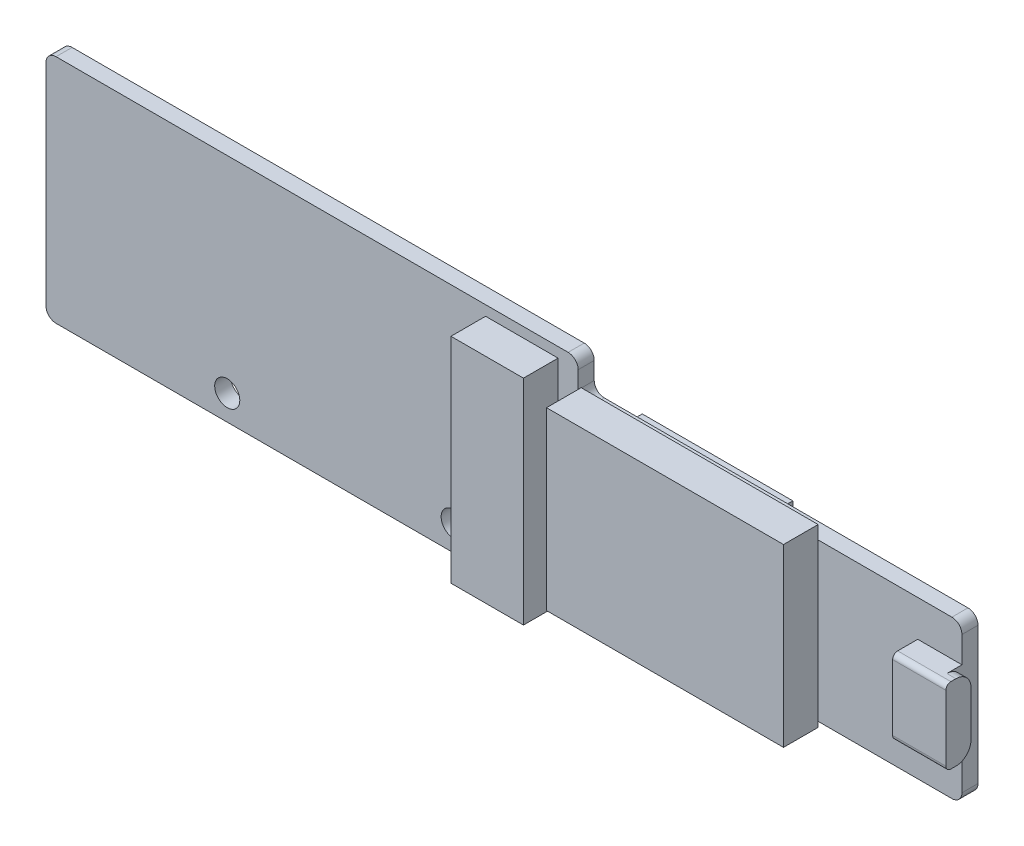
SolidWorks part; units mm, degrees
ref_plane "Front Plane" through (0, 0, 0) normal (0, 0, 1) x (1, 0, 0)
ref_plane "Top Plane" through (0, 0, 0) normal (0, 1, 0) x (1, 0, 0)
ref_plane "Right Plane" through (0, 0, 0) normal (1, 0, 0) x (0, 0, -1)
sketch "Sketch1" plane through (0, 0, 0) normal (0, 0, 1) x (1, 0, 0)
  line L0 (53, 19.27) -> (63.0723, 19.27) construction
  line L1 (0, 0) -> (53, 0)
  line L2 (0, 0) -> (0, 23)
  line L3 (0, 23) -> (53, 23)
  line L4 (53, 0) -> (53, 3.62)
  line L5 (47.5491, 11.445) -> (74.8048, 11.445) construction
  line L6 (53, 3.62) -> (63.0723, 3.62) construction
  line L7 (53, 19.27) -> (53, 23)
  line L8 (53, 19.27) -> (91.22, 19.27)
  line L10 (53, 3.62) -> (91.22, 3.62)
  line L11 (91.22, 19.27) -> (91.22, 3.62)
  circle A0 centre (40.6, 2.5) radius 1.25
  circle A1 centre (18.05, 2.5) radius 1.25
  dimension "D8" = 2.5
  dimension "D9" = 12.4
  dimension "D10" = 22.55
  dimension "D11" = 2.5
  dimension "D12" = 12.4
  dimension "D1" = 3.73
  dimension "D2" = 91.22
  dimension "D3" = 53
  dimension "D4" = 23
  dimension "D5" = 15.65
  dimension "D6" = 3.62
  dimension "D7" = 19.38
extrude "Boss-Extrude2" add sketch "Sketch1" along normal blind 1.6
sketch "Sketch2" plane through (0, 0, 0) normal (0, 0, -1) x (-1, 0, 0)
  line L0 (-91.22, 3.62) -> (-91.22, 19.27) construction
  line L1 (-72.12, 19.12) -> (-57.12, 19.12)
  line L2 (-72.12, 19.12) -> (-72.12, 3.77)
  line L3 (-72.12, 3.77) -> (-57.12, 3.77)
  line L4 (-57.12, 19.12) -> (-57.12, 3.77)
  line L5 (-72.12, 19.12) -> (-57.12, 3.77) construction
  line L6 (-72.12, 3.77) -> (-57.12, 19.12) construction
  line L7 (-91.22, 19.27) -> (-53, 19.27) construction
  line L8 (-53, 3.62) -> (-91.22, 3.62) construction
  point P0 (-64.62, 11.445)
  dimension "D1" = 34.1
  dimension "D2" = 15.5
  dimension "D3" = 0.15
  dimension "D4" = 0.15
extrude "Boss-Extrude3" add sketch "Sketch2" along normal blind 0.66
sketch "Sketch3" plane through (0, 0, 1.6) normal (0, 0, 1) x (1, 0, 0)
  line L1 (86.82, 15.66) -> (92.12, 15.66)
  line L2 (86.82, 15.66) -> (86.82, 8.12)
  line L3 (86.82, 8.12) -> (92.12, 8.12)
  line L4 (92.12, 15.66) -> (92.12, 8.12)
  line L5 (86.82, 15.66) -> (92.12, 8.12) construction
  line L6 (86.82, 8.12) -> (92.12, 15.66) construction
  line L7 (91.22, 19.27) -> (53, 19.27) construction
  line L9 (91.22, 3.62) -> (91.22, 19.27) construction
  point P0 (89.47, 11.89)
  dimension "D1" = 7.54
  dimension "D2" = 5.3
  dimension "D3" = 11.15
  dimension "D4" = 0.9
extrude "Boss-Extrude4" add sketch "Sketch3" along normal blind 2.5
fillet "Fillet1" radius 0.5 2 edges at (89.47, 8.12, 4.1) (89.47, 15.66, 4.1)
fillet "Fillet2" radius 1.5 2 edges at (91.67, 8.12, 1.6) (91.67, 15.66, 1.6)
sketch "Sketch4" plane through (0, 0, 0) normal (0, 0, -1) x (-1, 0, 0)
  line L0 (-4.4, 15.24) -> (0.9, 15.24)
  line L1 (-4.4, 15.24) -> (-4.4, 7.7)
  line L2 (-4.4, 7.7) -> (0.9, 7.7)
  line L3 (0.9, 15.24) -> (0.9, 7.7)
  line L4 (-4.4, 15.24) -> (0.9, 7.7) construction
  line L5 (-4.4, 7.7) -> (0.9, 15.24) construction
  line L6 (-53, 23) -> (0, 23) construction
  line L7 (0, 23) -> (0, 0) construction
  point P0 (-1.75, 11.47)
  dimension "D1" = 15.3
  dimension "D2" = 5.3
  dimension "D3" = 7.54
  dimension "D4" = 0.9
extrude "Boss-Extrude5" add sketch "Sketch4" along normal blind 2.5
fillet "Fillet3" radius 0.5 2 edges at (1.75, 7.7, -2.5) (1.75, 15.24, -2.5)
fillet "Fillet4" radius 1.5 2 edges at (-0.45, 7.7, 0) (-0.45, 15.24, 0)
sketch "Sketch5" plane through (0, 0, 1.6) normal (0, 0, 1) x (1, 0, 0)
  line L0 (53, 23) -> (0, 23) construction
  line L1 (43.78, 22) -> (51, 22)
  line L2 (43.78, 22) -> (43.78, 0.7)
  line L3 (43.78, 0.7) -> (51, 0.7)
  line L4 (51, 22) -> (51, 0.7)
  line L5 (43.78, 22) -> (51, 0.7) construction
  line L6 (43.78, 0.7) -> (51, 22) construction
  line L7 (53.3, 20.6) -> (76.9, 20.6)
  line L8 (53.3, 20.6) -> (53.3, 3.1)
  line L9 (53.3, 3.1) -> (76.9, 3.1)
  line L10 (76.9, 20.6) -> (76.9, 3.1)
  line L11 (53.3, 20.6) -> (76.9, 3.1) construction
  line L12 (53.3, 3.1) -> (76.9, 20.6) construction
  line L13 (53, 0) -> (53, 3.62) construction
  point P0 (47.39, 11.35)
  point P5 (65.1, 11.85)
  dimension "D1" = 7.22
  dimension "D2" = 21.3
  dimension "D3" = 22.3
  dimension "D4" = 2
  dimension "D5" = 2.3
  dimension "D6" = 23.6
  dimension "D7" = 17.5
  dimension "D8" = 2.4
extrude "Boss-Extrude6" add sketch "Sketch5" along normal blind 3.45
fillet "Fillet5" radius 1 8 edges at (91.22, 3.62, 0.8) (91.22, 19.27, 0.8) (0, 23, 0.8) (0, 0, 0.8) (53, 0, 0.8) (53, 23, 0.8) (53, 19.27, 0.8) (53, 3.62, 0.8)
